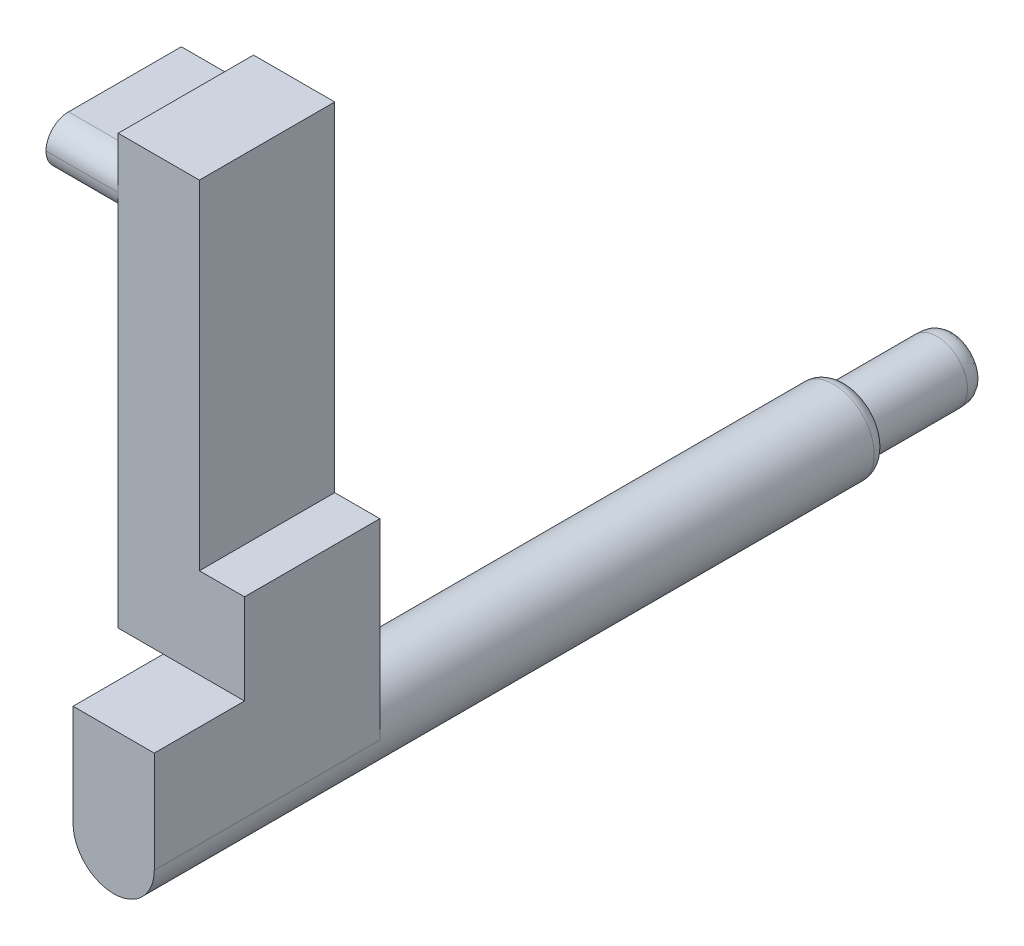
SolidWorks part; units mm, degrees
material "ABS"
ref_plane "Alzado" through (0, 0, 0) normal (0, 0, 1) x (1, 0, 0)
ref_plane "Planta" through (0, 0, 0) normal (0, 1, 0) x (1, 0, 0)
ref_plane "Vista lateral" through (0, 0, 0) normal (1, 0, 0) x (0, 0, -1)
sketch "Croquis1" plane through (0, 0, 0) normal (0, 0, 1) x (1, 0, 0)
  circle A4 centre (-6.3971, 9.5757) radius 0.675
  dimension "D1" = 1.35
extrude "Saliente-Extruir1" add sketch "Croquis1" against normal blind 2.4
fillet "Redondeo1" radius 0.4 1 edges at (-5.7221, 9.5757, -2.4) conic radius 0.2 tangent propagation no
sketch "Croquis2" plane through (0, 0, 0) normal (0, 0, 1) x (1, 0, 0)
  circle A5 centre (-6.3971, 9.5757) radius 0.9
  dimension "D1" = 1.8
extrude "Saliente-Extruir2" add sketch "Croquis2" along normal blind 12.25
sketch "Croquis3" plane through (0, 0, 12.25) normal (0, 0, 1) x (1, 0, 0)
  line L0 (-7.2971, 9.5757) -> (-5.4971, 9.5757)
  circle A0 centre (-6.3971, 9.5757) radius 0.9
  circle A1 centre (-6.3971, 9.5757) radius 0.9 construction
  circle M2 centre (-6.3971, 9.5757) radius 0.9
  dimension "D1" = 1.8
extrude "Saliente-Extruir3" add sketch "Croquis3" along normal blind 2 contours L0 M2 region at (-6.3971, 9.1937, 12.25)
sketch "Croquis4" plane through (0, 9.5757, 0) normal (0, 1, 0) x (1, 0, 0)
  line L0 (-6.3971, -9.45) -> (-6.3971, -14.2003) construction
  line L1 (-7.2971, -14.25) -> (-5.4971, -14.25) construction
  line L2 (-6.3971, -14.2003) -> (-6.3971, -14.25) construction
  line L3 (-5.4971, -14.25) -> (-7.2971, -14.25) construction
  line L4 (-7.2971, -14.25) -> (-7.2971, -12.25) construction
  line L5 (-7.2971, -12.25) -> (-7.2971, -14.25)
  line L6 (-7.2971, -14.25) -> (-5.4971, -14.25)
  line L9 (-7.2971, -12.25) -> (-5.4971, -12.25)
  line L10 (-5.4971, -14.25) -> (-5.4971, -12.25)
  line L13 (-7.2971, -12.25) -> (-5.4971, -12.25) construction
  point P2 (-6.3971, -12.25)
  line M8 (-5.4971, -12.25) -> (-7.2971, -12.25)
  line M9 (-7.2971, -12.25) -> (-7.2971, -14.25)
  line M11 (-5.4971, -14.25) -> (-5.4971, -12.25)
  dimension "D1" = 2
extrude "Saliente-Extruir4" add sketch "Croquis4" along normal blind 4.25 contours L10 L9 M11 | M11 M8 M9 | L9 L5 M9 | L6 M11 M9 | L6 M9 M11 | L6 M9 | L6 M11 | L6 M11 | L6 M9 region at (-6.3971, 9.5757, 13.25)
sketch "Croquis6" plane through (-7.2971, 0, 0) normal (-1, 0, 0) x (0, 0, 1)
  line L1 (14.25, 13.8257) -> (12.25, 13.8257)
  line L2 (14.25, 13.8257) -> (14.25, 11.8257)
  line L3 (14.25, 11.8257) -> (12.25, 11.8257)
  line L4 (12.25, 13.8257) -> (12.25, 11.8257)
  line L5 (12.25, 13.8257) -> (12.25, 9.5757) construction
  line L8 (12.25, 13.8257) -> (14.25, 13.8257) construction
  dimension "D1" = 2
extrude "Saliente-Extruir5" add sketch "Croquis6" along normal blind 1
sketch "Croquis7" plane through (0, 13.8257, 0) normal (0, 1, 0) x (1, 0, 0)
  line L0 (-5.4971, -12.25) -> (-8.2971, -12.25) construction
  line L2 (-8.2971, -12.25) -> (-6.4971, -12.25)
  line L5 (-8.2971, -12.25) -> (-8.2971, -14.25)
  line L7 (-8.2971, -14.25) -> (-8.2971, -12.25)
  line L12 (-8.2971, -12.25) -> (-6.4971, -12.25)
  line L13 (-6.4971, -14.25) -> (-6.4971, -12.25)
  line L14 (-8.2971, -14.25) -> (-6.4971, -14.25)
  line L15 (-6.4971, -12.25) -> (-6.4971, -14.25)
  point P7 (-6.4971, -13.25)
  line M5 (-5.4971, -12.25) -> (-8.2971, -12.25)
  line M6 (-8.2971, -12.25) -> (-8.2971, -14.25)
  line M7 (-8.2971, -14.25) -> (-5.4971, -14.25)
  dimension "D2" = 1.8
extrude "Saliente-Extruir6" add sketch "Croquis7" along normal blind 7.5 contours L13 M7 M5 M6 region at (-7.3971, 13.8257, 13.25)
sketch "Croquis9" plane through (0, 0, 12.25) normal (0, 0, -1) x (-1, 0, 0)
  line L0 (8.2971, 19.3857) -> (6.4971, 19.3857) construction
  line L1 (8.2971, 21.3257) -> (8.2971, 11.8257) construction
  line L2 (6.4971, 21.3257) -> (6.4971, 13.8257) construction
  line L3 (6.4971, 21.3257) -> (8.2971, 21.3257) construction
  line L4 (8.2971, 20.6857) -> (9.8971, 20.6857)
  line L5 (8.2971, 20.6857) -> (8.2971, 19.6857)
  line L6 (8.2971, 19.6857) -> (9.8971, 19.6857)
  line L7 (9.8971, 20.6857) -> (9.8971, 19.6857)
  point P10 (9.0971, 20.6857)
  point P11 (9.8971, 20.1857)
  dimension "D1" = 0.3
  dimension "D2" = 1
  dimension "D3" = 1.6
  dimension "D4" = 0.64
extrude "Saliente-Extruir7" add sketch "Croquis9" against normal blind 2
fillet "Redondeo2" radius 0.5 2 edges at (-9.0971, 20.6857, 14.25) (-9.0971, 19.6857, 14.25) first distance on face at (-7.6304, 16.079, 14.25)
sketch "Croquis10" plane through (0, 0, 12.25) normal (0, 0, -1) x (-1, 0, 0)
  line L143 (7.2971, 9.5757) -> (7.2971, 11.8257)
  line L144 (5.4971, 13.8257) -> (5.4971, 9.5757)
  line L145 (6.4971, 13.8257) -> (5.4971, 13.8257)
  line L146 (7.2971, 11.8257) -> (8.2971, 11.8257)
  line L147 (8.2971, 11.8257) -> (8.2971, 19.6857)
  line L148 (6.4971, 21.3257) -> (6.4971, 13.8257)
  line L149 (8.2971, 21.3257) -> (6.4971, 21.3257)
  line L150 (8.2971, 20.6857) -> (8.2971, 21.3257)
  line L151 (9.8971, 20.6857) -> (8.2971, 20.6857)
  line L152 (9.8971, 19.6857) -> (9.8971, 20.6857)
  line L153 (8.2971, 19.6857) -> (9.8971, 19.6857)
  line L154 (7.2971, 9.5757) -> (7.2971, 11.8257)
  line L155 (5.4971, 13.8257) -> (5.4971, 9.5757)
  line L156 (6.4971, 13.8257) -> (5.4971, 13.8257)
  line L157 (7.2971, 11.8257) -> (8.2971, 11.8257)
  line L158 (8.2971, 11.8257) -> (8.2971, 19.6857)
  line L159 (6.4971, 21.3257) -> (6.4971, 13.8257)
  line L160 (8.2971, 21.3257) -> (6.4971, 21.3257)
  line L161 (8.2971, 20.6857) -> (8.2971, 21.3257)
  line L162 (9.8971, 20.6857) -> (8.2971, 20.6857)
  line L163 (9.8971, 19.6857) -> (9.8971, 20.6857)
  line L164 (8.2971, 19.6857) -> (9.8971, 19.6857)
  arc A7 (7.2971, 9.5757) -> (5.4971, 9.5757) centre (6.3971, 9.5757) ccw
  arc A8 (7.2971, 9.5757) -> (5.4971, 9.5757) centre (6.3971, 9.5757) ccw
  dimension "D1" = 0
extrude "Saliente-Extruir8" add sketch "Croquis10" along normal blind 1
sketch "Croquis11" plane through (0, 0, 14.25) normal (0, 0, 1) x (1, 0, 0)
  line L1 (-7.2971, 11.8257) -> (-5.4971, 11.8257)
  line L2 (-7.2971, 11.8257) -> (-7.2971, 9.5757)
  line L4 (-5.4971, 11.8257) -> (-5.4971, 9.5757)
  arc A0 (-7.2971, 9.5757) -> (-5.4971, 9.5757) centre (-6.3971, 9.5757) ccw
extrude "Saliente-Extruir9" add sketch "Croquis11" along normal blind 2
fillet "Redondeo3" radius 0.3 1 edges at (-5.4971, 9.5757, 0)
